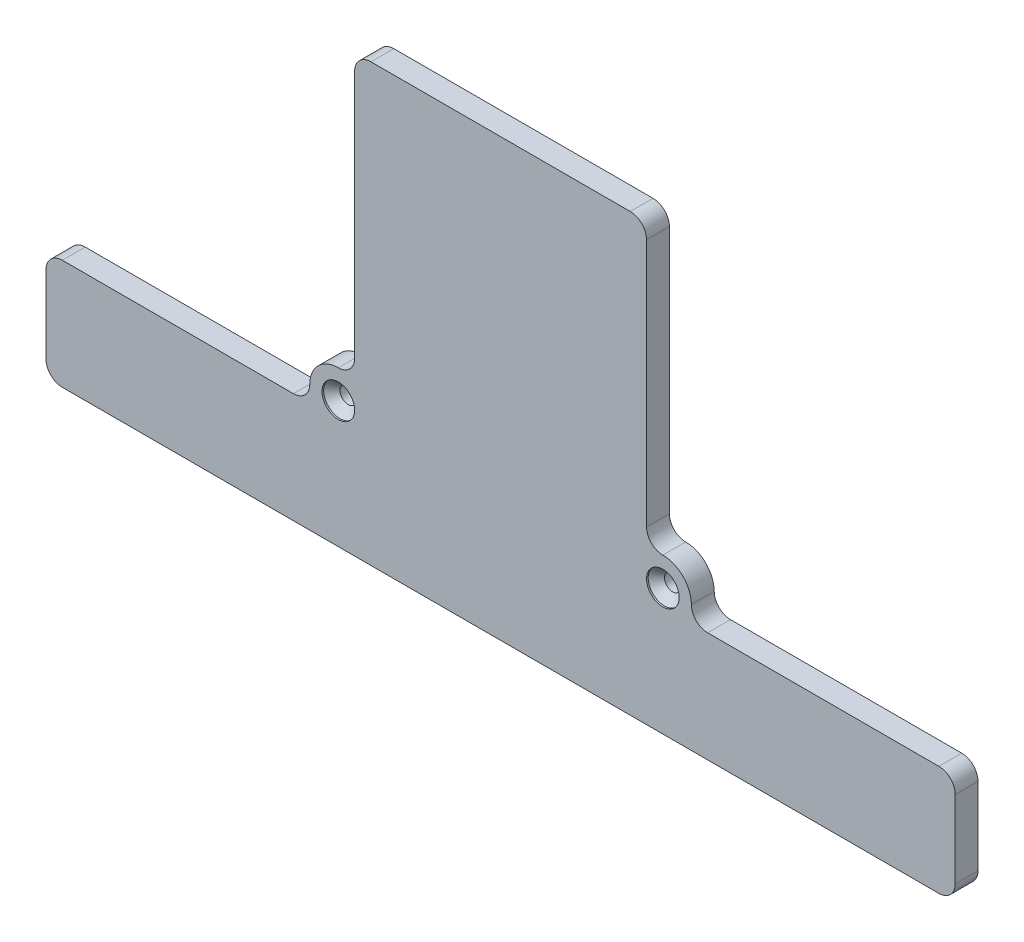
SolidWorks part; units mm, degrees
ref_plane "Front Plane" through (0, 0, 0) normal (0, 0, 1) x (1, 0, 0)
ref_plane "Top Plane" through (0, 0, 0) normal (0, 1, 0) x (1, 0, 0)
ref_plane "Right Plane" through (0, 0, 0) normal (1, 0, 0) x (0, 0, -1)
sketch "Sketch1" plane through (0, 0, 0) normal (0, 0, 1) x (1, 0, 0)
  line L8 (-53.75, -26.75) -> (53.75, -26.75)
  line L9 (55.75, -24.75) -> (55.75, -15.25)
  line L10 (53.75, -13.25) -> (25.4, -13.25)
  line L11 (17.9, -5.75) -> (17.9, 24.75)
  line L12 (15.9, 26.75) -> (-15.9, 26.75)
  line L13 (-17.9, 24.75) -> (-17.9, -5.75)
  line L14 (-25.4, -13.25) -> (-53.75, -13.25)
  line L15 (-55.75, -15.25) -> (-55.75, -24.75)
  line L16 (-53.75, -26.75) -> (53.75, -26.75)
  line L17 (55.75, -24.75) -> (55.75, -15.25)
  line L18 (53.75, -13.25) -> (25.4, -13.25)
  line L19 (17.9, -5.75) -> (17.9, 24.75)
  line L20 (15.9, 26.75) -> (-15.9, 26.75)
  line L21 (-17.9, 24.75) -> (-17.9, -5.75)
  line L22 (-25.4, -13.25) -> (-53.75, -13.25)
  line L23 (-55.75, -15.25) -> (-55.75, -24.75)
  arc A12 (53.75, -26.75) -> (55.75, -24.75) centre (53.75, -24.75) ccw
  arc A13 (55.75, -15.25) -> (53.75, -13.25) centre (53.75, -15.25) ccw
  arc A14 (23.4, -11.25) -> (25.4, -13.25) centre (25.4, -11.25) ccw
  arc A15 (23.4, -11.25) -> (19.9, -7.75) centre (19.9, -11.25) ccw
  arc A16 (17.9, -5.75) -> (19.9, -7.75) centre (19.9, -5.75) ccw
  arc A17 (17.9, 24.75) -> (15.9, 26.75) centre (15.9, 24.75) ccw
  arc A18 (-15.9, 26.75) -> (-17.9, 24.75) centre (-15.9, 24.75) ccw
  arc A19 (-19.9, -7.75) -> (-17.9, -5.75) centre (-19.9, -5.75) ccw
  arc A20 (-19.9, -7.75) -> (-23.4, -11.25) centre (-19.9, -11.25) ccw
  arc A21 (-25.4, -13.25) -> (-23.4, -11.25) centre (-25.4, -11.25) ccw
  arc A22 (-53.75, -13.25) -> (-55.75, -15.25) centre (-53.75, -15.25) ccw
  arc A23 (-55.75, -24.75) -> (-53.75, -26.75) centre (-53.75, -24.75) ccw
  arc A24 (53.75, -26.75) -> (55.75, -24.75) centre (53.75, -24.75) ccw
  arc A25 (55.75, -15.25) -> (53.75, -13.25) centre (53.75, -15.25) ccw
  arc A26 (23.4, -11.25) -> (25.4, -13.25) centre (25.4, -11.25) ccw
  arc A27 (23.4, -11.25) -> (19.9, -7.75) centre (19.9, -11.25) ccw
  arc A28 (17.9, -5.75) -> (19.9, -7.75) centre (19.9, -5.75) ccw
  arc A29 (17.9, 24.75) -> (15.9, 26.75) centre (15.9, 24.75) ccw
  arc A30 (-15.9, 26.75) -> (-17.9, 24.75) centre (-15.9, 24.75) ccw
  arc A31 (-19.9, -7.75) -> (-17.9, -5.75) centre (-19.9, -5.75) ccw
  arc A32 (-19.9, -7.75) -> (-23.4, -11.25) centre (-19.9, -11.25) ccw
  arc A33 (-25.4, -13.25) -> (-23.4, -11.25) centre (-25.4, -11.25) ccw
  arc A34 (-53.75, -13.25) -> (-55.75, -15.25) centre (-53.75, -15.25) ccw
  arc A35 (-55.75, -24.75) -> (-53.75, -26.75) centre (-53.75, -24.75) ccw
  dimension "D1" = 0
extrude "Boss-Extrude1" add sketch "Sketch1" along normal blind 2.8
sketch "Sketch3" plane through (0, 0, 2.8) normal (0, 0, 1) x (1, 0, 0)
  line L0 (0, 32.8811) -> (0, -41.8665) construction
  circle A0 centre (-19.9, -11.25) radius 1
  arc A1 (-19.9, -7.75) -> (-23.4, -11.25) centre (-19.9, -11.25) ccw construction
  circle A2 centre (19.9, -11.25) radius 1
  dimension "D1" = 2
extrude "Cut-Extrude1" cut sketch "Sketch3" against normal up to next
hole_wizard "CSK for M2 Flat Head Machine Screw1" positions "Sketch5" profile "Sketch4" countersink size "M2" standard "ANSI Metric" end condition through all
sketch "Sketch5" plane through (0, 0, 2.8) normal (0, 0, 1) x (1, 0, 0)
  point P0 (-19.9, -11.25)
  point P3 (19.9, -11.25)
sketch "Sketch4" plane through (-19.9, -11.25, 2.8) normal (1, 0, 0) x (0, -1, 0)
  line L0 (0, 0) -> (0, 2.8)
  line L1 (0, 2.8) -> (1, 2.8)
  line L2 (1, 2.8) -> (1, 1.2)
  line L3 (1, 1.2) -> (2, 0.2)
  line L4 (2, 0.2) -> (2, 0)
  line L6 (2, 0) -> (0, 0)
  line L7 (-1, 1.2) -> (-2, 0.2) construction
  line L11 (0, -6.35) -> (0, 107.95) construction
  dimension "Thru Hole Dia." = 2
  dimension "Thru Hole Depth" = 2.8
  dimension "C'Sink Dia." = 4
  dimension "C'Sink Angle" = 90
  dimension "Head Clearance" = 0.2
